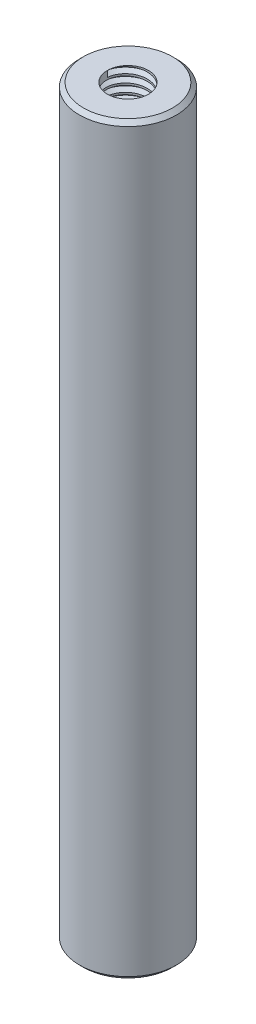
SolidWorks part; units mm, degrees
material "6061-T6 (SS)"
ref_plane "Alzado" through (0, 0, 0) normal (0, 0, 1) x (1, 0, 0)
ref_plane "Planta" through (0, 0, 0) normal (0, 1, 0) x (1, 0, 0)
ref_plane "Vista lateral" through (0, 0, 0) normal (1, 0, 0) x (0, 0, -1)
sketch "Croquis2" plane through (0, 0, 0) normal (0, 1, 0) x (1, 0, 0)
  circle A0 centre (0, 0) radius 4.7625
  dimension "D1" = 9.525
extrude "Saliente-Extruir1" add sketch "Croquis2" along normal mid plane 73.025
chamfer "Chaflán1" distance 0.3969 angle 45 2 edges at (0, -36.5125, 4.7625) (0, 36.5125, 4.7625)
sketch "Croquis3" plane through (0, 0, 0) normal (0, 1, 0) x (1, 0, 0)
  circle A0 centre (0, 0) radius 2.0193
  dimension "D1" = 4.0386
extrude "Tap Hole 1" cut sketch "Croquis3" against normal blind 19.05 from surface starting at face at (0, 36.5125, 4.3656)
extrude "Tap Hole 2" cut sketch "Croquis3<2>" along normal blind 19.05 from surface starting at face at (0, -36.5125, 4.3656)
sketch "Croquis3<2>" plane through (0, 0, 0) normal (0, 1, 0) x (1, 0, 0) same geometry as "Croquis3"
sketch "Croquis4" plane through (0, 0, 0) normal (0, 1, 0) x (1, 0, 0)
  circle A0 centre (0, 0) radius 2.4892
  dimension "D1" = 4.9784
extrude "Clearance Hole" [suppressed] cut sketch "Croquis4" against normal through all both and the other way through all
thread "Rosca1" pitch 0.7937 method cut profile "Perfil de rosca1" start angle 0, offset 0, length 0, pitch 0.7937, diameter 4.0386
ref_plane "Plano1" through (2.0193, -36.5125, 0) normal (0, 0, 1) x (1, 0, 0)
sketch "Perfil de rosca1" plane through (2.0193, -36.5125, 0) normal (0, 0, 1) x (1, 0, 0)
  line L0 (0, 0) -> (0, 0.7937) construction
  line L1 (0, 0) -> (0.4296, 0.248)
  line L2 (0.4296, 0.248) -> (0.4296, 0.3473)
  line L3 (0.4296, 0.3473) -> (0, 0.5953)
  line L4 (0.4296, 0.2977) -> (0, 0.2977) construction
  line L11 (0, 0) -> (0, 0.5953)
  point P2 (0, 0)
  dimension "Pitch" = 0.7937
  dimension "Profile_Angle" = 60
  dimension "Profile_Land" = 0.0992
  dimension "Profile_Height" = 0.4296
thread "Rosca2" pitch 0.7937 method cut profile "Perfil de rosca2" start angle 0, offset 0, length 0, pitch 0.7937, diameter 4.0386
ref_plane "Plano2" through (-2.0193, 36.5125, 0) normal (0, 0, 1) x (-1, 0, 0)
sketch "Perfil de rosca2" plane through (-2.0193, 36.5125, 0) normal (0, 0, 1) x (-1, 0, 0)
  line L0 (0, 0) -> (0, 0.7937) construction
  line L1 (0, 0) -> (0.4296, 0.248)
  line L2 (0.4296, 0.248) -> (0.4296, 0.3473)
  line L3 (0.4296, 0.3473) -> (0, 0.5953)
  line L4 (0.4296, 0.2977) -> (0, 0.2977) construction
  line L11 (0, 0) -> (0, 0.5953)
  point P2 (0, 0)
  dimension "Pitch" = 0.7937
  dimension "Profile_Angle" = 60
  dimension "Profile_Land" = 0.0992
  dimension "Profile_Height" = 0.4296
equation "\"OD\"= 0.375pulgadas"
equation "\"Largo\"= 2.875pulgadas"
equation "\"Tap Hole\"= IIF ( \"OD\" = 0.375pulgadas , 0.1590pulgadas , 0.201pulgadas )"
equation "\"Spacer Hole\"= IIF ( \"OD\" = 0.375pulgadas , 0.196pulgadas , 0.257pulgadas )"
equation "\"D1@Croquis2\"=\"OD\""
equation "\"D1@Saliente-Extruir1\"=\"Largo\""
equation "\"D1@Croquis3\"=\"Tap Hole\""
equation "\"D1@Croquis4\"=\"Spacer Hole\""
